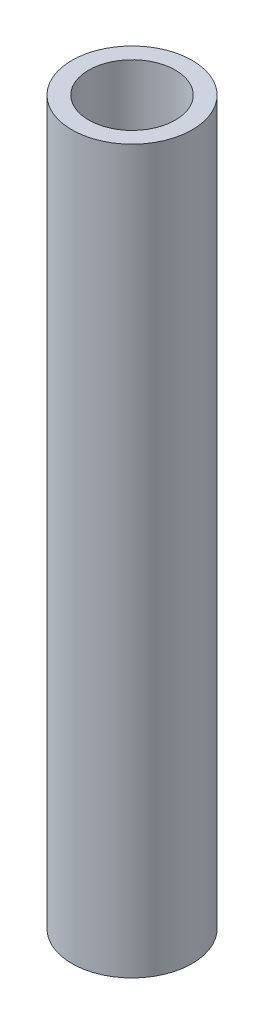
SolidWorks part; units mm, degrees
material "AISI Type 316L stainless steel"
ref_plane "Front Plane" through (0, 0, 0) normal (0, 0, 1) x (1, 0, 0)
ref_plane "Top Plane" through (0, 0, 0) normal (0, 1, 0) x (1, 0, 0)
ref_plane "Right Plane" through (0, 0, 0) normal (1, 0, 0) x (0, 0, -1)
sketch "Sketch1" plane through (0, 0, 0) normal (0, 1, 0) x (1, 0, 0)
  circle A0 centre (0, 0) radius 3.175
  circle A1 centre (0, 0) radius 2.286
  dimension "D1" = 6.35
  dimension "D2" = 4.572
extrude "Boss-Extrude1" add sketch "Sketch1" along normal blind 38.1
